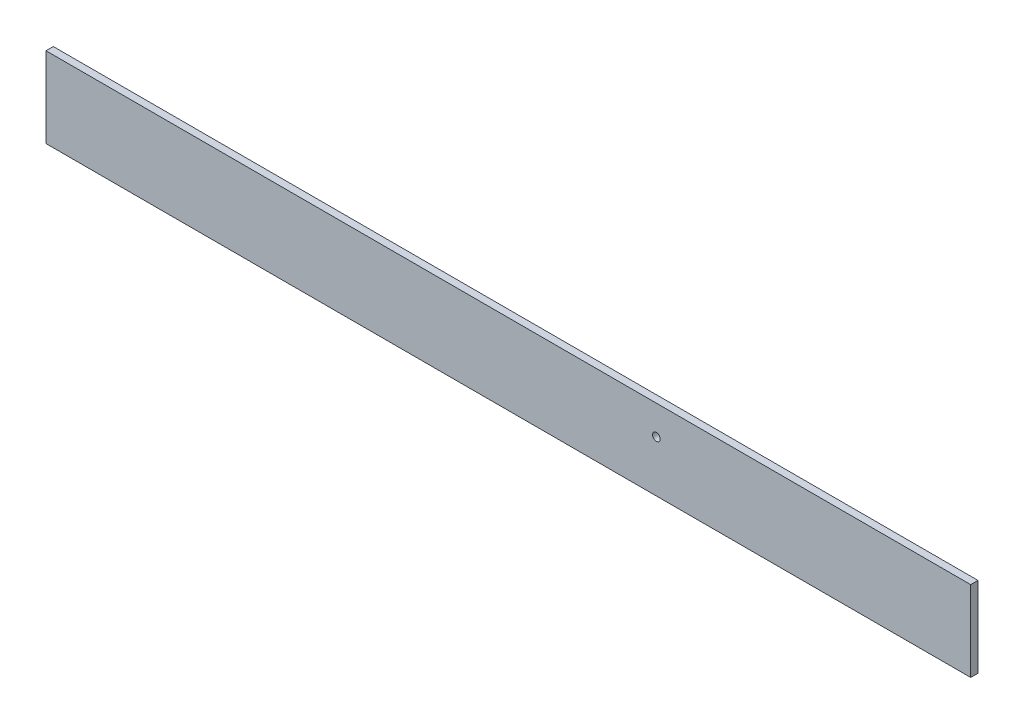
SolidWorks part; units mm, degrees
ref_plane "Front Plane" through (0, 0, 0) normal (0, 0, 1) x (1, 0, 0)
ref_plane "Top Plane" through (0, 0, 0) normal (0, 1, 0) x (1, 0, 0)
ref_plane "Right Plane" through (0, 0, 0) normal (1, 0, 0) x (0, 0, -1)
sketch "Sketch2" plane through (0, 0, 0) normal (0, 0, 1) x (1, 0, 0)
  line L1 (-253, -22) -> (253, -22)
  line L2 (-253, -22) -> (-253, 22)
  line L3 (-253, 22) -> (253, 22)
  line L4 (253, -22) -> (253, 22)
  line L5 (-253, -22) -> (253, 22) construction
  line L6 (-253, 22) -> (253, -22) construction
  circle A0 centre (81, 6) radius 2.1 construction
  circle A1 centre (81, 6) radius 2.1
  point P0 (0, 0)
  dimension "D1" = 44
  dimension "D2" = 506
extrude "Boss-Extrude1" add sketch "Sketch2" along normal blind 4
